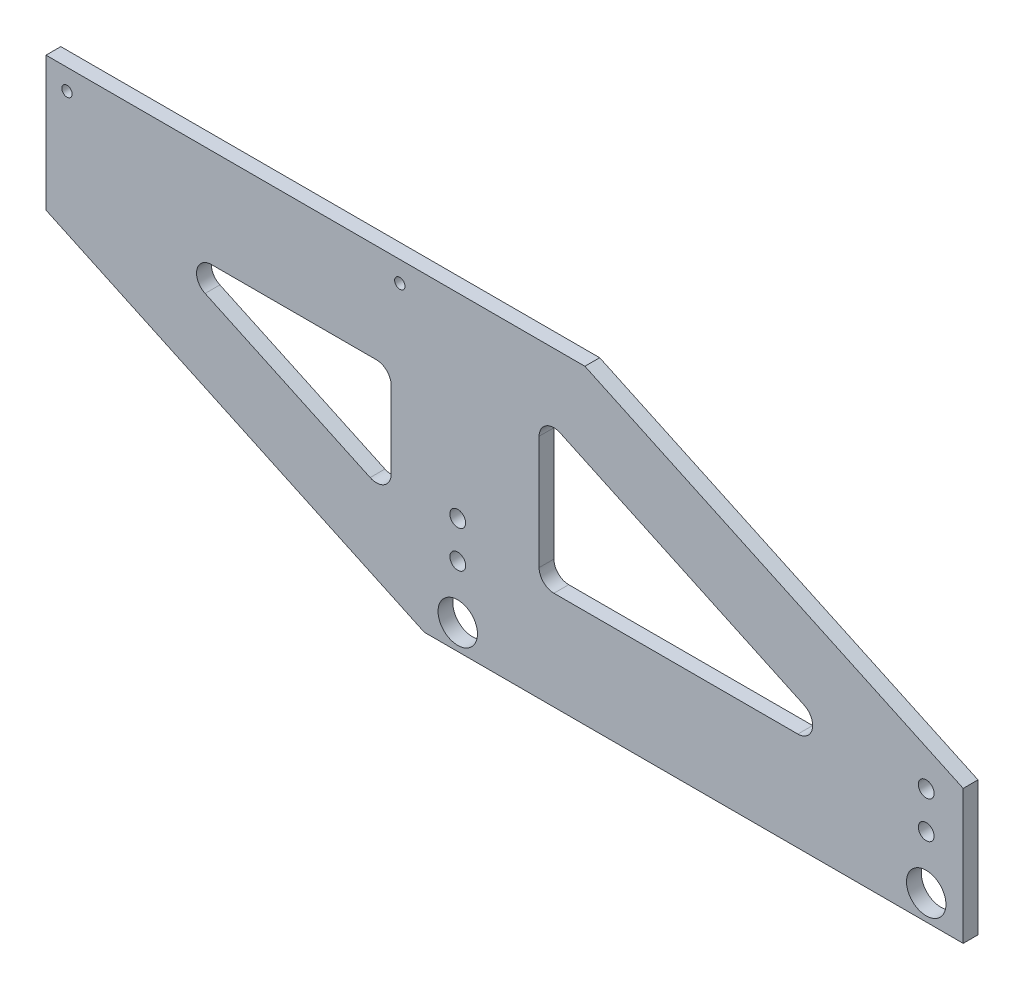
SolidWorks part; units mm, degrees
ref_plane "Front Plane" through (0, 0, 0) normal (0, 0, 1) x (1, 0, 0)
ref_plane "Top Plane" through (0, 0, 0) normal (0, 1, 0) x (1, 0, 0)
ref_plane "Right Plane" through (0, 0, 0) normal (1, 0, 0) x (0, 0, -1)
sketch "Sketch1" plane through (0, 0, 0) normal (0, 0, 1) x (1, 0, 0)
  line L0 (102.5, 14.1154) -> (102.5, 28.65) construction
  line L1 (-83.5, 74.1154) -> (25.7792, 74.1154)
  line L2 (-83.5, 74.1154) -> (-83.5, 46.8909)
  line L3 (-6.7792, 11.1154) -> (102.5, 11.1154)
  line L4 (102.5, 38.3399) -> (102.5, 11.1154)
  line L6 (-16.5, 11.1154) -> (-23.5, 11.1154) construction
  line L7 (-83.5, 71.1154) -> (-83.5, 14.1154) construction
  line L8 (-80.5, 74.1154) -> (-10.5, 74.1154) construction
  line L9 (25.7792, 74.1154) -> (102.5, 38.3399)
  line L10 (-83.5, 46.8909) -> (-6.7792, 11.1154)
  line L11 (-63.5, 54.1154) -> (-13.5, 54.1154)
  line L12 (-13.5, 54.1154) -> (-13.5, 30.8)
  line L13 (-13.5, 30.8) -> (-63.5, 54.1154)
  line L14 (16.5, 61.8917) -> (16.5, 31.1154)
  line L15 (16.5, 31.1154) -> (82.5, 31.1154)
  line L16 (82.5, 31.1154) -> (16.5, 61.8917)
  circle A0 centre (-79.25, 69.9154) radius 1.05
  circle A1 centre (-11.75, 69.9154) radius 1.05
  circle A2 centre (0, 16.2019) radius 4
  circle A3 centre (95, 16.2019) radius 4
  circle A4 centre (95, 27) radius 1.6
  circle A5 centre (95, 34.5) radius 1.6
  circle A6 centre (0, 34.5) radius 1.6
  circle A7 centre (0, 27) radius 1.6
  dimension "D1" = 3.2
  dimension "D2" = 8
  dimension "D3" = 2.1
  dimension "D4" = 115
  dimension "D5" = 15
  dimension "D6" = 15
  dimension "D7" = 20
  dimension "D8" = 20
  dimension "D9" = 50
  dimension "D10" = 20
  dimension "D11" = 30
extrude "Extrude1" add sketch "Sketch1" along normal blind 3
fillet "Fillet1" radius 3 6 edges at (82.5, 31.1154, 1.5) (16.5, 31.1154, 1.5) (16.5, 61.8917, 1.5) (-13.5, 30.8, 1.5) (-63.5, 54.1154, 1.5) (-13.5, 54.1154, 1.5)
